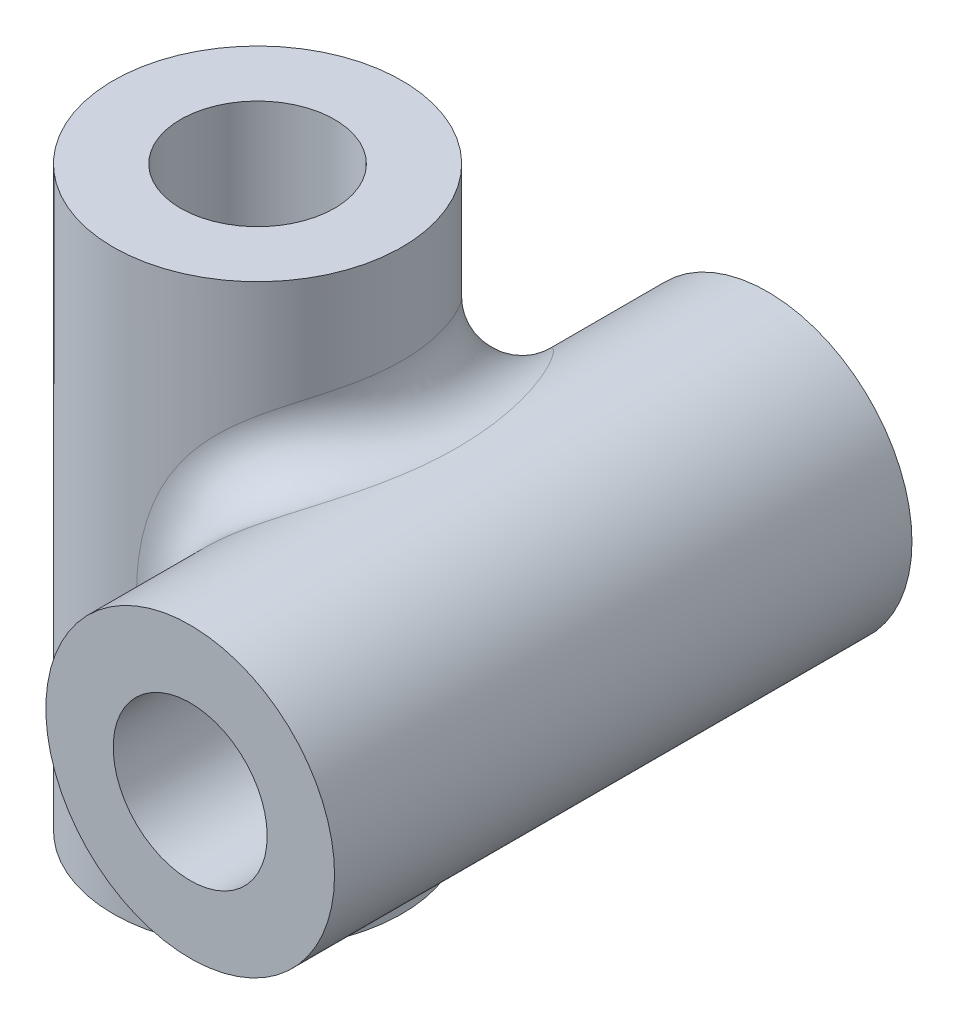
SolidWorks part; units mm, degrees
ref_plane "Front Plane" through (0, 0, 0) normal (0, 0, 1) x (1, 0, 0)
ref_plane "Top Plane" through (0, 0, 0) normal (0, 1, 0) x (1, 0, 0)
ref_plane "Right Plane" through (0, 0, 0) normal (1, 0, 0) x (0, 0, -1)
sketch "Sketch1" plane through (0, 0, 0) normal (0, 1, 0) x (1, 0, 0)
  circle A0 centre (0, 0) radius 8
  circle A1 centre (0, 0) radius 15
  dimension "D1" = 30
  dimension "D2" = 16
extrude "Boss-Extrude1" add sketch "Sketch1" along normal blind 60
sketch "Sketch2" plane through (0, 0, 0) normal (0, 0, 1) x (1, 0, 0)
  circle A0 centre (23, 30) radius 15
  circle A1 centre (23, 30) radius 8
  dimension "D2" = 30
  dimension "D3" = 16
  dimension "D1" = 23
extrude "Boss-Extrude2" add sketch "Sketch2" along normal mid plane 60
fillet "Fillet1" radius 5 1 edges at (8.3863, 33.3823, -12.4366) type face fillet first side face at (0, 60, 15) second side face at (38, 30, -30)
